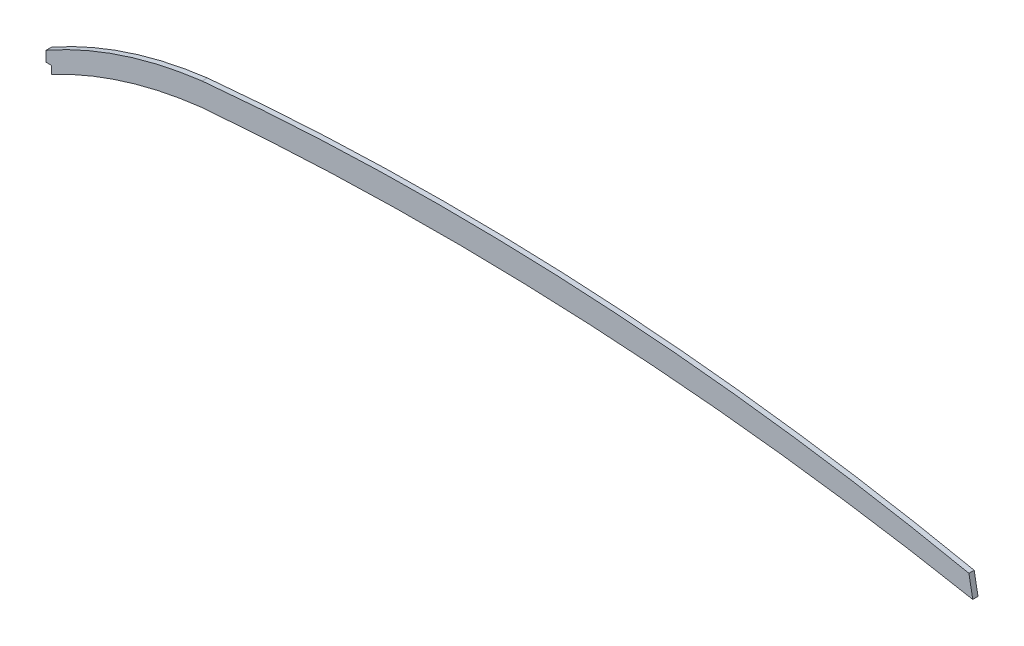
SolidWorks part; units mm, degrees
material "Balsa"
ref_plane "Front Plane" through (0, 0, 0) normal (0, 0, 1) x (1, 0, 0)
ref_plane "Top Plane" through (0, 0, 0) normal (0, 1, 0) x (1, 0, 0)
ref_plane "Right Plane" through (0, 0, 0) normal (1, 0, 0) x (0, 0, -1)
sketch "Sketch1" plane through (0, 0, 0) normal (0, 0, 1) x (1, 0, 0)
  line L2 (0, 0) -> (0, 169.3685) construction
  line L4 (93.98, 106.68) -> (556.5761, 106.68) construction
  line L9 (0, 106.68) -> (93.98, 106.68) construction
  line L14 (555.6382, 111.8229) -> (555.6382, 106.68) construction
  line L17 (555.6382, 111.8229) -> (557.917, 99.3265)
  line L19 (0, 106.68) -> (0, 93.98)
  line L20 (93.98, 137.668) -> (93.98, 123.7947) construction
  arc A6 (0, 106.68) -> (93.98, 137.668) centre (125.0054, -114.43) cw
  arc A8 (93.98, 137.668) -> (555.6382, 111.8229) centre (239.5165, -1398.7972) cw
  arc A9 (0, 93.98) -> (93.98, 123.7947) centre (122.3372, -128.6174) cw
  arc A25 (93.98, 123.7947) -> (557.917, 99.3265) centre (236.8486, -1577.8511) cw
  dimension "D4" = 254
  dimension "D2" = 93.98
  dimension "D8" = 1543.3426
  dimension "D9" = 100.334
  dimension "D3" = 30.988
  dimension "D12" = 254
  dimension "D14" = 1707.6328
  dimension "D1" = 106.68
  dimension "D5" = 462.5961
  dimension "D6" = 0.9378
  dimension "D7" = 5.1429
  dimension "D10" = 12.7025
  dimension "D11" = 12.7
  dimension "D13" = 13.8733
extrude "Boss-Extrude1" add sketch "Sketch1" against normal blind 3.175 contours A9 A25 L17 A8 A6 L19 region at (551.2665, 104.5698, 0)
sketch "Sketch2" plane through (0, 0, -3.175) normal (0, 0, -1) x (-1, 0, 0)
  line L0 (0, 0) -> (0, 93.98) construction
  line L4 (0, 93.98) -> (-3.3528, 93.98)
  line L5 (0, 93.98) -> (0, 100.457)
  line L6 (0, 100.457) -> (-3.3528, 100.457)
  line L7 (-3.3528, 93.98) -> (-3.3528, 100.457)
  dimension "D1" = 93.98
  dimension "D2" = 6.477
  dimension "D3" = 3.3528
extrude "Cut-Extrude1" cut sketch "Sketch2" against normal through all
equation "\"slotwidth\"=0.167708"
